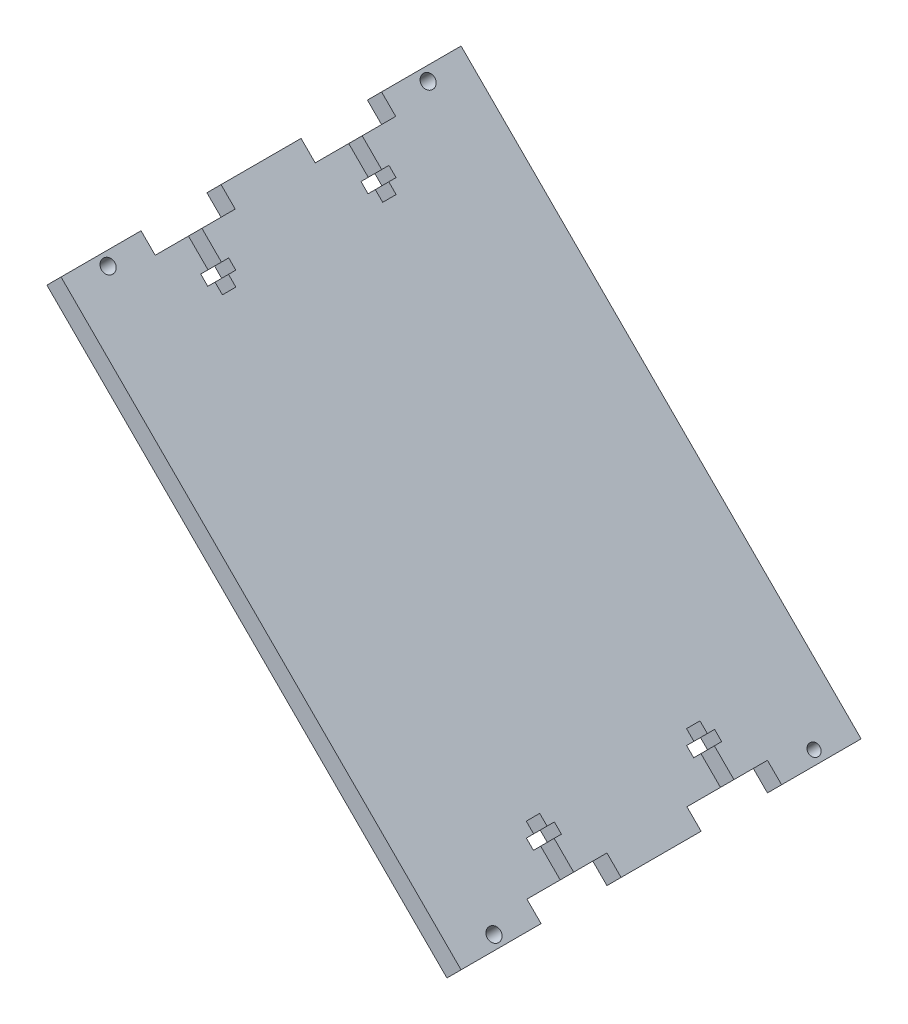
SolidWorks part; units mm, degrees
ref_plane "Front Plane" through (0, 0, 0) normal (0, 0, 1) x (1, 0, 0)
ref_plane "Top Plane" through (0, 0, 0) normal (0, 1, 0) x (1, 0, 0)
ref_plane "Right Plane" through (0, 0, 0) normal (1, 0, 0) x (0, 0, -1)
sketch "Sketch1" plane through (0, 0, 0) normal (0, 0, 1) x (1, 0, 0)
  line L0 (-127, 0) -> (0, -127)
  line L1 (-127, 0) -> (-122.5099, 4.4901)
  line L2 (0, -127) -> (4.4901, -122.5099)
  line L3 (-122.5099, 4.4901) -> (4.4901, -122.5099)
  dimension "D1" = 6.35
extrude "Boss-Extrude1" add sketch "Sketch1" along normal blind 127
sketch "Sketch2" plane through (-63.5, -63.5, 0) normal (-0.7071, -0.7071, 0) x (0, 0, 1)
  line L0 (127, 89.8026) -> (0, 89.8026) construction
  line L1 (101.6, 83.4526) -> (76.2, 83.4526)
  line L2 (101.6, 83.4526) -> (101.6, 89.8026)
  line L3 (101.6, 89.8026) -> (76.2, 89.8026)
  line L4 (76.2, 83.4526) -> (76.2, 89.8026)
  line L5 (76.2, 89.8026) -> (76.2, 83.4526) construction
  line L6 (127, -89.8026) -> (0, -89.8026) construction
  line L7 (50.8, 83.4526) -> (25.2406, 83.4526)
  line L8 (50.8, 83.4526) -> (50.8, 89.8026)
  line L9 (50.8, 89.8026) -> (25.2406, 89.8026)
  line L10 (25.2406, 83.4526) -> (25.2406, 89.8026)
  line L11 (101.6, -83.4526) -> (76.2, -83.4526)
  line L12 (101.6, -83.4526) -> (101.6, -89.8026)
  line L13 (101.6, -89.8026) -> (76.2, -89.8026)
  line L14 (76.2, -83.4526) -> (76.2, -89.8026)
  line L15 (76.2, -83.4526) -> (76.2, -89.8026) construction
  line L17 (50.8, -83.4526) -> (25.2406, -83.4526)
  line L18 (50.8, -83.4526) -> (50.8, -89.8026)
  line L19 (50.8, -89.8026) -> (25.2406, -89.8026)
  line L20 (25.2406, -83.4526) -> (25.2406, -89.8026)
extrude "Cut-Extrude1" cut sketch "Sketch2" against normal blind 6.35
sketch "Sketch3" plane through (-63.5, -63.5, 0) normal (-0.7071, -0.7071, 0) x (0, 0, 1)
  line L0 (88.9, 83.4526) -> (88.9, 43.5267) construction
  line L1 (76.2, 83.4526) -> (101.6, 83.4526) construction
  line L2 (38.0203, 83.4526) -> (38.0203, 48.0562) construction
  line L3 (25.2406, 83.4526) -> (50.8, 83.4526) construction
  line L4 (88.9, -83.4526) -> (88.9, -48.5744) construction
  line L5 (101.6, -83.4526) -> (76.2, -83.4526) construction
  line L6 (38.0203, -83.4526) -> (38.0203, -60.3513) construction
  line L7 (50.8, -83.4526) -> (25.2406, -83.4526) construction
  line L8 (76.2, 83.4526) -> (101.6, 83.4526) construction
  line L9 (101.6, -83.4526) -> (76.2, -83.4526) construction
  line B0 (91.0336, 83.4526) -> (86.7664, 83.4526)
  line B1 (86.7664, 71.5146) -> (84.455, 71.5146)
  line B2 (84.455, 71.5146) -> (84.455, 74.6896)
  line B3 (84.455, 74.6896) -> (86.7664, 74.6896)
  line B4 (86.7664, 74.6896) -> (86.7664, 83.4526)
  line B5 (86.7664, 71.5146) -> (86.7664, 68.2126)
  line B6 (86.7664, 68.2126) -> (91.0336, 68.2126)
  line B7 (91.0336, 71.5146) -> (91.0336, 68.2126)
  line B8 (91.0336, 74.6896) -> (91.0336, 83.4526)
  line B9 (93.345, 74.6896) -> (91.0336, 74.6896)
  line B10 (93.345, 71.5146) -> (93.345, 74.6896)
  line B11 (91.0336, 71.5146) -> (93.345, 71.5146)
  line B12 (40.1539, 83.4526) -> (35.8867, 83.4526)
  line B13 (35.8867, 71.5146) -> (33.5753, 71.5146)
  line B14 (33.5753, 71.5146) -> (33.5753, 74.6896)
  line B15 (33.5753, 74.6896) -> (35.8867, 74.6896)
  line B16 (35.8867, 74.6896) -> (35.8867, 83.4526)
  line B17 (35.8867, 71.5146) -> (35.8867, 68.2126)
  line B18 (35.8867, 68.2126) -> (40.1539, 68.2126)
  line B19 (40.1539, 71.5146) -> (40.1539, 68.2126)
  line B20 (40.1539, 74.6896) -> (40.1539, 83.4526)
  line B21 (42.4653, 74.6896) -> (40.1539, 74.6896)
  line B22 (42.4653, 71.5146) -> (42.4653, 74.6896)
  line B23 (40.1539, 71.5146) -> (42.4653, 71.5146)
  line B24 (86.7664, -83.4526) -> (91.0336, -83.4526)
  line B25 (91.0336, -71.5146) -> (93.345, -71.5146)
  line B26 (93.345, -71.5146) -> (93.345, -74.6896)
  line B27 (93.345, -74.6896) -> (91.0336, -74.6896)
  line B28 (91.0336, -74.6896) -> (91.0336, -83.4526)
  line B29 (91.0336, -71.5146) -> (91.0336, -68.2126)
  line B30 (91.0336, -68.2126) -> (86.7664, -68.2126)
  line B31 (86.7664, -71.5146) -> (86.7664, -68.2126)
  line B32 (86.7664, -74.6896) -> (86.7664, -83.4526)
  line B33 (84.455, -74.6896) -> (86.7664, -74.6896)
  line B34 (84.455, -71.5146) -> (84.455, -74.6896)
  line B35 (86.7664, -71.5146) -> (84.455, -71.5146)
  line B36 (35.8867, -83.4526) -> (40.1539, -83.4526)
  line B37 (40.1539, -71.5146) -> (42.4653, -71.5146)
  line B38 (42.4653, -71.5146) -> (42.4653, -74.6896)
  line B39 (42.4653, -74.6896) -> (40.1539, -74.6896)
  line B40 (40.1539, -74.6896) -> (40.1539, -83.4526)
  line B41 (40.1539, -71.5146) -> (40.1539, -68.2126)
  line B42 (40.1539, -68.2126) -> (35.8867, -68.2126)
  line B43 (35.8867, -71.5146) -> (35.8867, -68.2126)
  line B44 (35.8867, -74.6896) -> (35.8867, -83.4526)
  line B45 (33.5753, -74.6896) -> (35.8867, -74.6896)
  line B46 (33.5753, -71.5146) -> (33.5753, -74.6896)
  line B47 (35.8867, -71.5146) -> (33.5753, -71.5146)
sketch_block_instance "TSlot-1"
sketch_block "TSlot" parameters "D1"=3.302, "D2"=3.175
sketch_block_instance "TSlot-2"
sketch_block_instance "TSlot-3"
sketch_block_instance "TSlot-5"
extrude "Cut-Extrude2" cut sketch "Sketch3" against normal blind 6.35
sketch "Sketch4" plane through (-59.0099, -59.0099, 0) normal (0.7071, 0.7071, 0) x (0, 0, -1)
  line L0 (-116.4336, 83.4526) -> (-112.1664, 89.8026) construction
  line L1 (-127, 89.8026) -> (-101.6, 89.8026) construction
  line L2 (-112.1664, 83.4526) -> (-112.1664, 89.8026) construction
  line L3 (-112.1664, 83.4526) -> (-116.4336, 89.8026) construction
  line L4 (-116.4336, -83.4526) -> (-112.1664, -89.8026) construction
  line L5 (-127, -89.8026) -> (-101.6, -89.8026) construction
  line L6 (-112.1664, -83.4526) -> (-116.4336, -89.8026) construction
  line L7 (-116.4336, -83.4526) -> (-116.4336, -89.8026) construction
  line L8 (-14.8336, 83.4526) -> (-10.5664, 89.8026) construction
  line L9 (-25.2406, 89.8026) -> (0, 89.8026) construction
  line L10 (-10.5664, 83.4526) -> (-14.8336, 89.8026) construction
  line L11 (-14.8336, 83.4526) -> (-14.8336, 89.8026) construction
  line L12 (-14.8336, -83.4526) -> (-10.5664, -89.8026) construction
  line L13 (-25.2406, -89.8026) -> (0, -89.8026) construction
  line L14 (-10.5664, -83.4526) -> (-10.5664, -89.8026) construction
  line L15 (-10.5664, -83.4526) -> (-14.8336, -89.8026) construction
  line L16 (-14.8336, -83.4526) -> (-14.8336, -89.8026) construction
  circle A0 centre (-114.3, 86.6276) radius 2.0955
  circle A1 centre (-12.7, 86.6276) radius 2.0955
  circle A2 centre (-12.7, -86.6276) radius 1.8283
  circle A3 centre (-114.3, -86.6276) radius 2.0955
  dimension "D1" = 4.191
extrude "Cut-Extrude3" cut sketch "Sketch4" against normal blind 6.35
